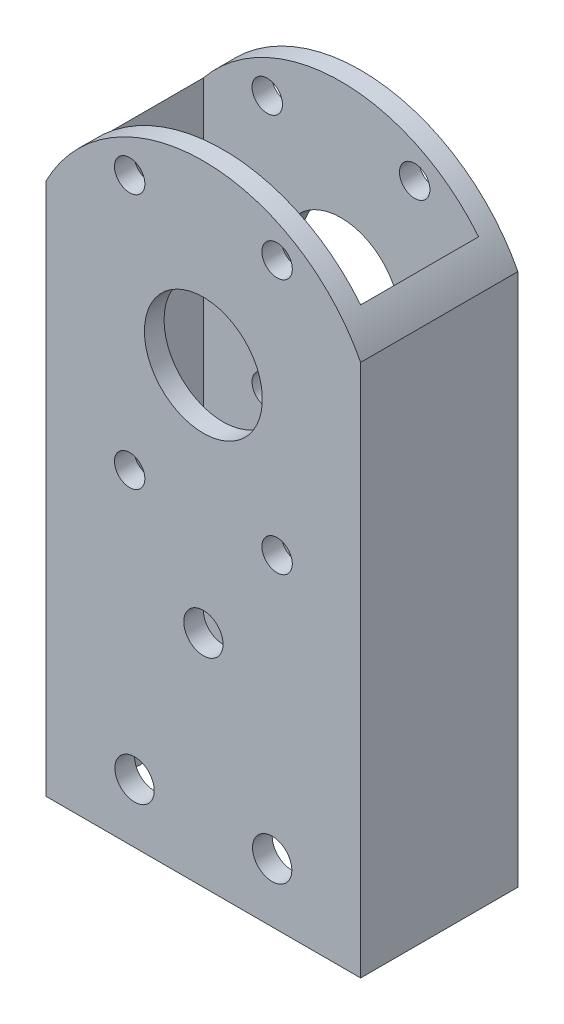
SolidWorks part; units mm, degrees
material "6061-T6 (SS)"
ref_plane "Front" through (0, 0, 0) normal (0, 0, 1) x (1, 0, 0)
ref_plane "Top" through (0, 0, 0) normal (0, 1, 0) x (1, 0, 0)
ref_plane "Right" through (0, 0, 0) normal (1, 0, 0) x (0, 0, -1)
sketch "Sketch1" plane through (0, 0, 0) normal (0, 1, 0) x (1, 0, 0)
  line L1 (-25.4, -12.7) -> (25.4, -12.7)
  line L2 (-25.4, -12.7) -> (-25.4, 12.7)
  line L3 (-25.4, 12.7) -> (25.4, 12.7)
  line L4 (25.4, -12.7) -> (25.4, 12.7)
  line L5 (-25.4, -12.7) -> (25.4, 12.7) construction
  line L6 (-25.4, 12.7) -> (25.4, -12.7) construction
  point P0 (0, 0)
  dimension "D1" = 25.4
  dimension "D2" = 50.8
extrude "Extrude-Thin1" add sketch "Sketch1" along normal blind 101.6 thin thin type one direction reverse wall 3.175
sketch "Sketch2" plane through (0, 0, -12.7) normal (0, 0, -1) x (-1, 0, 0)
  line L0 (0, 101.6) -> (0, 69.85)
  line L1 (-25.4, 101.6) -> (25.4, 101.6) construction
  line L3 (0, 60.325) -> (0, 79.375) construction
  circle A1 centre (0, 69.85) radius 23.8125
  circle A3 centre (0, 69.85) radius 9.525
  point P12 (0, 69.85)
  dimension "D1" = 19.05
  dimension "D3" = 47.625
  dimension "D2" = 31.75
hole_wizard "#10 (0.1935) Diameter Hole2" positions "Sketch5" profile "Sketch6" hole size "#10" standard "ANSI Inch" end condition through all
sketch "Sketch5" plane through (0, 0, -12.7) normal (0, 0, -1) x (-1, 0, 0)
  line L0 (0, 101.6) -> (0, 73.025)
  line L1 (-25.4, 101.6) -> (25.4, 101.6) construction
  line L3 (-11.9063, 93.6472) -> (11.9063, 93.6472)
  line L4 (-11.9063, 93.6472) -> (-11.9063, 52.4028)
  line L5 (-11.9063, 52.4028) -> (11.9063, 52.4028)
  line L6 (11.9063, 93.6472) -> (11.9063, 52.4028)
  circle A0 centre (0, 73.025) radius 23.8125
  point P21 (-11.9063, 93.6472)
  point P22 (11.9063, 93.6472)
  point P24 (11.9063, 52.4028)
  point P25 (-11.9063, 52.4028)
  dimension "D1" = 47.625
  dimension "D2" = 28.575
  dimension "D3" = 23.8125
sketch "Sketch6" plane through (11.9063, 52.4028, -12.7) normal (1, 0, 0) x (0, 1, 0)
  line L0 (0, 0) -> (0, 25.4)
  line L1 (0, 25.4) -> (2.4574, 25.4)
  line L2 (2.4574, 25.4) -> (2.4574, 0)
  line L5 (2.4574, 0) -> (0, 0)
  line L11 (0, -6.35) -> (0, 107.95) construction
  dimension "Thru Hole Dia." = 4.9149
  dimension "Thru Hole Depth" = 25.4
sketch "Sketch7" plane through (0, 0, -12.7) normal (0, 0, -1) x (-1, 0, 0)
  line L0 (-11.9063, 93.6472) -> (11.9063, 52.4028) construction
  circle A1 centre (0, 73.025) radius 9.525
  point P9 (0, 73.025)
  dimension "D1" = 19.05
extrude "Cut-Extrude2" cut sketch "Sketch7" against normal through all both
hole_wizard "1/4 (0.25) Diameter Hole1" positions "Sketch8" profile "Sketch9" hole size "1/4" standard "ANSI Inch" end condition through all
sketch "Sketch8" plane through (0, 0, 12.7) normal (0, 0, 1) x (1, 0, 0)
  line L2 (-25.4, 101.6) -> (-25.4, 0) construction
  line L4 (-25.4, 0) -> (25.4, 0) construction
  point P0 (-11.1125, 9.525)
  point P2 (11.1125, 9.525)
  point P14 (-109.1715, 68.7854)
  dimension "D1" = 22.225
  dimension "D2" = 14.2875
  dimension "D3" = 9.525
sketch "Sketch9" plane through (-11.1125, 9.525, 12.7) normal (1, 0, 0) x (0, -1, 0)
  line L0 (0, 0) -> (0, 25.4)
  line L1 (0, 25.4) -> (3.175, 25.4)
  line L2 (3.175, 25.4) -> (3.175, 0)
  line L5 (3.175, 0) -> (0, 0)
  line L11 (0, -6.35) -> (0, 107.95) construction
  dimension "Thru Hole Dia." = 6.35
  dimension "Thru Hole Depth" = 25.4
sketch "Sketch10" plane through (0, 0, -12.7) normal (0, 0, -1) x (-1, 0, 0)
  line L0 (-25.4, 86.1159) -> (-25.4, 101.6)
  line L1 (-25.4, 101.6) -> (25.4, 101.6)
  line L2 (25.4, 101.6) -> (25.4, 86.1159)
  line L3 (25.4, 101.6) -> (25.4, 0) construction
  arc A0 (25.4, 86.1159) -> (-25.4, 86.1159) centre (0, 73.025) ccw
  line M13 (25.4, 0) -> (25.4, 101.6)
  line M14 (25.4, 101.6) -> (-25.4, 101.6)
  line M15 (-25.4, 101.6) -> (-25.4, 0)
extrude "Cut-Extrude3" cut sketch "Sketch10" against normal through all contours A0 L1 M15 | A0 M13 M14 region at (-19.4433, 97.2944, -12.7) region at (19.4433, 97.2944, -12.7)
sketch "Sketch13" plane through (0, 0, 12.7) normal (0, 0, 1) x (1, 0, 0)
  line L4 (-25.4, 86.1159) -> (-25.4, 0) construction
  point P0 (0, 35.56)
  dimension "D1" = 35.56
  dimension "D2" = 25.4
hole_wizard "1/4 (0.25) Diameter Hole2" positions "Sketch13" profile "Sketch12" hole size "1/4" standard "ANSI Inch" end condition through all
sketch "Sketch12" plane through (0, 35.56, 12.7) normal (1, 0, 0) x (0, -1, 0)
  line L0 (0, 0) -> (0, 25.4)
  line L1 (0, 25.4) -> (3.175, 25.4)
  line L2 (3.175, 25.4) -> (3.175, 0)
  line L5 (3.175, 0) -> (0, 0)
  line L11 (0, -6.35) -> (0, 107.95) construction
  dimension "Thru Hole Dia." = 6.35
  dimension "Thru Hole Depth" = 25.4
